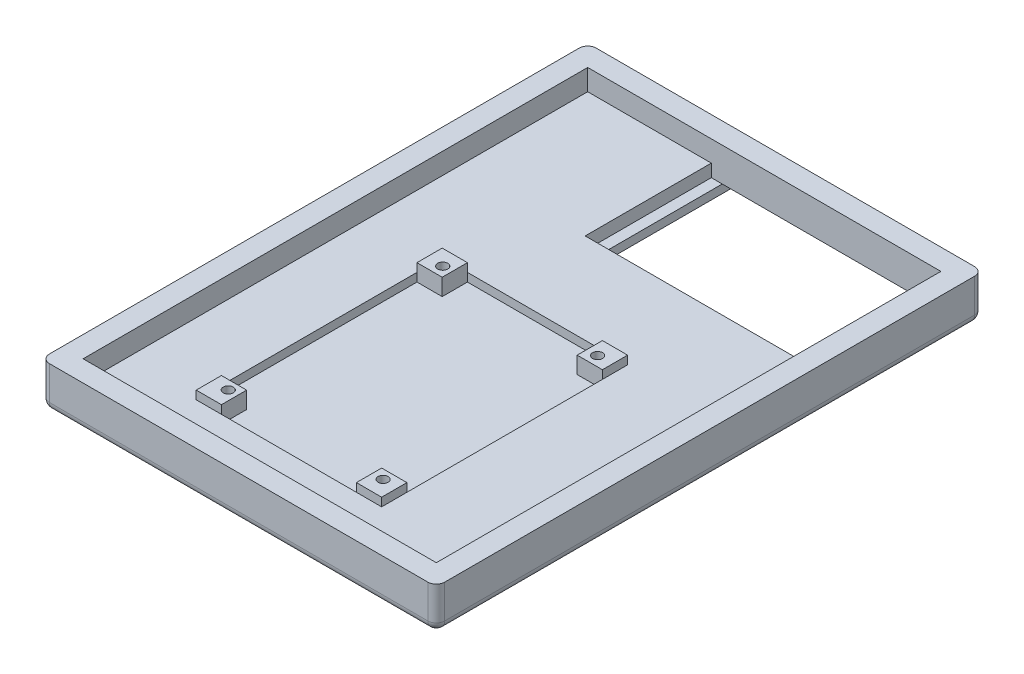
SolidWorks part; units mm, degrees
ref_plane "Front Plane" through (0, 0, 0) normal (0, 0, 1) x (1, 0, 0)
ref_plane "Top Plane" through (0, 0, 0) normal (0, 1, 0) x (1, 0, 0)
ref_plane "Right Plane" through (0, 0, 0) normal (1, 0, 0) x (0, 0, -1)
sketch "Sketch1" plane through (0, 0, 0) normal (0, 1, 0) x (1, 0, 0)
  line L1 (0, 0) -> (94, 0)
  line L2 (0, 0) -> (0, 130)
  line L3 (0, 130) -> (94, 130)
  line L4 (94, 0) -> (94, 130)
  dimension "D1" = 94
  dimension "D2" = 130
extrude "Boss-Extrude1" add sketch "Sketch1" along normal blind 5
sketch "Sketch2" plane through (0, 5, 0) normal (0, 1, 0) x (1, 0, 0)
  line L4 (5, 125) -> (5, 5)
  line L5 (5, 5) -> (89, 5)
  line L6 (89, 5) -> (89, 125)
  line L7 (89, 125) -> (5, 125)
  line L8 (0, 130) -> (0, 0)
  line L9 (0, 0) -> (94, 0)
  line L10 (94, 0) -> (94, 130)
  line L11 (94, 130) -> (0, 130)
  line L12 (0, 130) -> (0, 0)
  line L13 (0, 0) -> (94, 0)
  line L14 (94, 0) -> (94, 130)
  line L15 (94, 130) -> (0, 130)
  dimension "D1" = 0
  dimension "D2" = 5
extrude "Boss-Extrude2" add sketch "Sketch2" along normal blind 5
fillet "Fillet1" radius 2 8 edges at (0, 5, -130) (0, 5, 0) (94, 5, 0) (47, 0, 0) (0, 0, -65) (94, 0, -65) (47, 0, -130) (94, 5, -130)
sketch "Sketch3" plane through (0, 5, 0) normal (0, 1, 0) x (1, 0, 0)
  line L0 (5, 125) -> (5, 5) construction
  line L1 (21.9, 73.5) -> (66, 73.5)
  line L2 (21.9, 73.5) -> (21.9, 15)
  line L3 (21.9, 15) -> (66, 15)
  line L4 (66, 73.5) -> (66, 15)
  line L11 (5, 5) -> (89, 5) construction
  dimension "D1" = 58.5
  dimension "D2" = 44.1
  dimension "D3" = 16.9
  dimension "D4" = 10
extrude "Cut-Extrude1" cut sketch "Sketch3" against normal blind 2
sketch "Sketch5" plane through (0, 3, 0) normal (0, 1, 0) x (1, 0, 0)
  line L0 (66, 73.5) -> (21.9, 73.5) construction
  line L1 (21.9, 73.5) -> (27.9, 73.5)
  line L2 (21.9, 73.5) -> (21.9, 67.5)
  line L3 (21.9, 67.5) -> (27.9, 67.5)
  line L4 (27.9, 73.5) -> (27.9, 67.5)
  line L5 (60, 73.5) -> (66, 73.5)
  line L6 (60, 73.5) -> (60, 67.5)
  line L7 (60, 67.5) -> (66, 67.5)
  line L8 (66, 73.5) -> (66, 67.5)
  line L9 (60, 21) -> (66, 21)
  line L10 (60, 21) -> (60, 15)
  line L11 (60, 15) -> (66, 15)
  line L12 (66, 21) -> (66, 15)
  line L13 (21.9, 21) -> (27.9, 21)
  line L14 (21.9, 21) -> (21.9, 15)
  line L15 (21.9, 15) -> (27.9, 15)
  line L16 (27.9, 21) -> (27.9, 15)
  line L17 (21.9, 73.5) -> (21.9, 15) construction
  line L18 (66, 15) -> (66, 73.5) construction
  line L19 (21.9, 15) -> (66, 15) construction
  dimension "D1" = 6
  dimension "D2" = 6
  dimension "D3" = 6
  dimension "D4" = 6
  dimension "D5" = 6
  dimension "D6" = 6
  dimension "D7" = 6
  dimension "D8" = 6
extrude "Boss-Extrude4" add sketch "Sketch5" along normal blind 4
sketch "Sketch7" plane through (0, 7, 0) normal (0, 1, 0) x (1, 0, 0)
  circle A0 centre (25.6846, 69.839) radius 1.2
  circle A1 centre (62.5146, 69.839) radius 1.2
  circle A2 centre (62.5146, 18.8358) radius 1.2
  circle A3 centre (25.6846, 18.8358) radius 1.2
extrude "Cut-Extrude2" cut sketch "Sketch7" against normal blind 3
sketch "Sketch8" plane through (0, 5, 0) normal (0, 1, 0) x (1, 0, 0)
  line L1 (34.4, 95) -> (89, 95)
  line L2 (34.4, 95) -> (34.4, 125)
  line L3 (34.4, 125) -> (89, 125)
  line L4 (89, 95) -> (89, 125)
  line L5 (89, 5) -> (89, 125) construction
  line L6 (89, 125) -> (5, 125) construction
  dimension "D1" = 30
  dimension "D2" = 54.6
extrude "Cut-Extrude3" cut sketch "Sketch8" against normal blind 3
sketch "Sketch9" plane through (0, 2, 0) normal (0, 1, 0) x (1, 0, 0)
  line L0 (34.4, 95) -> (89, 95) construction
  line L1 (37, 96.5) -> (86.4, 96.5)
  line L2 (37, 96.5) -> (37, 123.5)
  line L3 (37, 123.5) -> (86.4, 123.5)
  line L4 (86.4, 96.5) -> (86.4, 123.5)
  line L5 (89, 125) -> (34.4, 125) construction
  line L6 (34.4, 125) -> (34.4, 95) construction
  line L8 (89, 5) -> (89, 125) construction
  dimension "D1" = 1.5
  dimension "D2" = 1.5
  dimension "D3" = 2.6
  dimension "D4" = 2.6
extrude "Cut-Extrude4" cut sketch "Sketch9" against normal blind 2
sketch "Sketch10" plane through (0, 0, 0) normal (0, -1, 0) x (1, 0, 0)
  line L1 (86.4, -123.5) -> (37, -123.5)
  line L2 (86.4, -123.5) -> (86.4, -130.1195)
  line L3 (86.4, -130.1195) -> (37, -130.1195)
  line L4 (37, -123.5) -> (37, -130.1195)
  line L5 (37, -123.5) -> (37, -96.5) construction
  line L6 (86.4, -96.5) -> (86.4, -123.5) construction
  line L7 (86.4, -123.5) -> (37, -123.5) construction
extrude "Cut-Extrude5" cut sketch "Sketch10" against normal blind 2
sketch "Sketch11" plane through (0, 0, -96.5) normal (0, 0, -1) x (-1, 0, 0)
  line L0 (-37, 0) -> (-86.4, 0) construction
  line L1 (-64.2, 1.5) -> (-59.2, 1.5)
  line L2 (-64.2, 1.5) -> (-64.2, 0.5)
  line L3 (-64.2, 0.5) -> (-59.2, 0.5)
  line L4 (-59.2, 1.5) -> (-59.2, 0.5)
  line L5 (-86.4, 0) -> (-86.4, 2) construction
  point P6 (-61.7, 0)
  point P7 (-61.7, 0.5)
  point P10 (-86.4, 1)
  point P11 (-64.2, 1)
  dimension "D1" = 5
  dimension "D2" = 1
extrude "Cut-Extrude6" cut sketch "Sketch11" against normal blind 3
